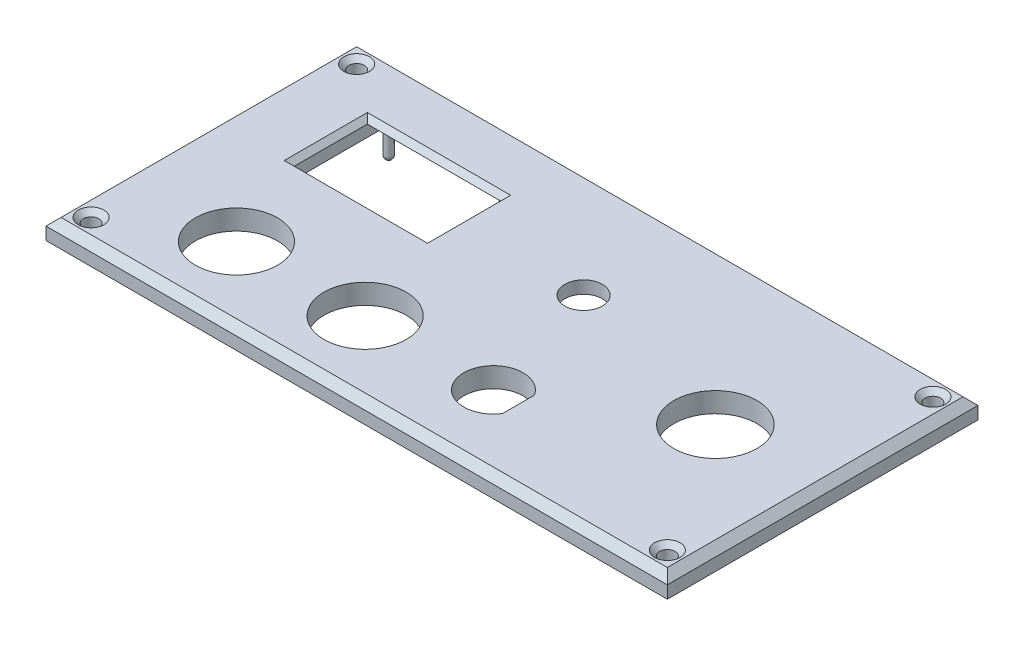
SolidWorks part; units mm, degrees
note: The reader was unsure of these and kept them because the rebuilt part matched: shared geometry of "Sketch2<3>", "Sketch2<4>", "Sketch2<5>".
ref_plane "Front Plane" through (0, 0, 0) normal (0, 0, 1) x (1, 0, 0)
ref_plane "Top Plane" through (0, 0, 0) normal (0, 1, 0) x (1, 0, 0)
ref_plane "Right Plane" through (0, 0, 0) normal (1, 0, 0) x (0, 0, -1)
sketch "Sketch2" plane through (0, 0, 0) normal (0, 1, 0) x (1, 0, 0)
  line L0 (-55.3925, 57.5) -> (145.2566, 57.5) construction
  line L1 (0, 0) -> (124, 0)
  line L2 (0, 0) -> (0, 62)
  line L3 (0, 62) -> (124, 62)
  line L4 (124, 0) -> (124, 62)
  line L5 (4.5, 83.9208) -> (4.5, -17.3547) construction
  line L6 (-55.3925, 4.5) -> (145.2566, 4.5) construction
  line L7 (119.5, 83.9208) -> (119.5, -17.3547) construction
  line L8 (3.6, 51.9) -> (3.6, 10.1)
  line L9 (-12.602, 31) -> (135.6682, 31) construction
  line L10 (135.6682, 31) -> (20.7736, 31) construction
  line L11 (10.1, 58.4) -> (113.9, 58.4)
  line L12 (3.6, 51.9) -> (10.1, 51.9)
  line L13 (3.6, 51.9) -> (3.6, 10.1)
  line L14 (3.6, 10.1) -> (10.1, 10.1)
  line L15 (120.4, 51.9) -> (120.4, 10.1)
  line L16 (62, 70.8482) -> (62, -22.3665) construction
  line L17 (113.9, 51.9) -> (120.4, 51.9)
  line L18 (10.1, 58.4) -> (113.9, 58.4)
  line L19 (10.1, 58.4) -> (10.1, 51.9)
  line L20 (10.1, 3.6) -> (113.9, 3.6)
  line L21 (113.9, 58.4) -> (113.9, 51.9)
  line L22 (10.1, 10.1) -> (10.1, 3.6)
  line L23 (113.9, 10.1) -> (120.4, 10.1)
  line L24 (113.9, 10.1) -> (113.9, 3.6)
  line L25 (79.4542, 18.0185) -> (79.4542, 11.6606)
  line L26 (14.9397, 49.1974) -> (41.5397, 49.1974)
  line L27 (14.9397, 49.1974) -> (14.9397, 34.5974)
  line L28 (14.9397, 34.5974) -> (41.5397, 34.5974)
  line L29 (41.5397, 49.1974) -> (41.5397, 34.5974)
  line L31 (14.2397, 53.7974) -> (42.2397, 53.7974)
  line L32 (14.2397, 53.7974) -> (14.2397, 25.4474)
  line L33 (14.2397, 25.4474) -> (42.2397, 25.4474)
  line L34 (42.2397, 53.7974) -> (42.2397, 25.4474)
  line L35 (60.4783, 47.2032) -> (73.6783, 47.2032)
  line L36 (60.4783, 47.2032) -> (60.4783, 33.2032)
  line L37 (60.4783, 33.2032) -> (73.6783, 33.2032)
  line L38 (73.6783, 47.2032) -> (73.6783, 33.2032)
  line L39 (60.4783, 47.2032) -> (73.6783, 33.2032) construction
  line L40 (60.4783, 33.2032) -> (73.6783, 47.2032) construction
  circle A0 centre (4.5, 57.5) radius 1.55
  circle A1 centre (119.5, 4.5) radius 1.55
  circle A2 centre (119.5, 57.5) radius 1.55
  circle A3 centre (4.5, 4.5) radius 1.55
  circle A4 centre (102.5933, 31) radius 8.3
  circle A5 centre (102.5933, 31) radius 12.375
  circle A6 centre (67.0783, 40.2032) radius 8.2
  circle A7 centre (67.0783, 40.2032) radius 3.75
  circle A8 centre (39.7997, 51.7093) radius 0.8
  circle A9 centre (39.7997, 28.4093) radius 0.8
  circle A10 centre (16.6797, 28.4093) radius 0.8
  circle A11 centre (16.6797, 51.7093) radius 0.8
  circle A12 centre (74.4542, 14.8396) radius 5.925
  circle A13 centre (74.4542, 14.8396) radius 7.25
  circle A14 centre (48.8465, 14.8396) radius 8.2
  circle A15 centre (48.8465, 14.8396) radius 8.95
  circle A16 centre (23.1711, 14.8396) radius 8.2
  circle A17 centre (23.1711, 14.8396) radius 8.95
  point P25 (0, 31)
  point P27 (3.6, 31)
  point P34 (62, 62)
  point P35 (62, 58.4)
  point P60 (64.5191, 39.9792)
  point P61 (28.2397, 34.5974)
  point P77 (28.2397, 53.7974)
  point P78 (28.2397, 49.1974)
  point P79 (67.0783, 40.2032)
  dimension "D7" = 3.1
  dimension "D14" = 16.6
  dimension "D15" = 24.75
  dimension "D16" = 16.4
  dimension "D17" = 7.5
  dimension "D20" = 1.6
  dimension "D21" = 23.3
  dimension "D25" = 11.85
  dimension "D26" = 14.5
  dimension "D28" = 28.35
  dimension "D22" = 13.2
  dimension "D1" = 62
  dimension "D2" = 124
  dimension "D3" = 4.5
  dimension "D4" = 4.5
  dimension "D5" = 4.5
  dimension "D6" = 4.5
  dimension "D8" = 41.8
  dimension "D9" = 3.6
  dimension "D10" = 3.6
  dimension "D11" = 103.8
  dimension "D12" = 3.6
  dimension "D13" = 3.6
  dimension "D18" = 14.6
  dimension "D19" = 26.6
  dimension "D23" = 11.56
  dimension "D24" = 11.56
  dimension "D27" = 5
  dimension "D29" = 28
  dimension "D30" = 4.6
  dimension "D31" = 14
extrude "Boss-Extrude1" add sketch "Sketch2" along normal blind 4 contours L24 L23 L15 L17 L21 L11 L19 L12 L8 L14 L22 L20 A17 A15 A13 A11 A10 A9 A8 A7 A5 L26 L29 L28 L27 | L1 L4 L3 L2 A3 A2 A1 A0 L23 L24 L20 L22 L14 L8 L12 L19 L11 L21 L17 L15 | A10 | A9 | A8 | A11 | L34 L31 L32 L33 A11 A10 A9 A8 L26 L29 L28 L27 | A13 A12 | A5 A4 | A7 A6 | A15 A14 | A17 A16 | L25 A12 | L36 A6 | L38 A6 | L35 A6 | L37 A6 | A6 L36 L37 | A6 L38 L35 | A6 L35 L36 | L37 A6 L38 L35 L36 A7
chamfer "Chamfer1" distance 1.5 angle 45 4 edges at (124, 4, -31) (62, 4, -62) (62, 4, 0) (0, 4, -31)
chamfer "Chamfer2" distance 1 angle 45 5 edges at (119.5, 4, -55.95) (119.5, 0, -55.95) (4.5, 4, -2.95) (119.5, 4, -2.95) (4.5, 4, -55.95)
extrude "Boss-Extrude2" add sketch "Sketch2<3>" against normal blind 3.5 contours A10 | A11 | A9 | A8
sketch "Sketch2<3>" plane through (0, 0, 0) normal (0, 1, 0) x (1, 0, 0) same geometry as "Sketch2"
fillet "Fillet1" radius 0.8 4 edges at (39.7997, -3.5, -27.6093) (16.6797, -3.5, -27.6093) (16.6797, -3.5, -50.9093) (39.7997, -3.5, -50.9093)
extrude "Cut-Extrude1" cut sketch "Sketch2<4>" along normal blind 3 contours L34 L31 L32 L33 A11 A10 A9 A8 L26 L29 L28 L27
sketch "Sketch2<4>" plane through (0, 0, 0) normal (0, 1, 0) x (1, 0, 0) same geometry as "Sketch2"
chamfer "Chamfer3" distance 1 angle 45 4 edges at (28.2397, 4, -34.5974) (41.5397, 4, -41.8974) (14.9397, 4, -41.8974) (28.2397, 4, -49.1974)
extrude "Cut-Extrude4" cut sketch "Sketch2<5>" along normal blind 1.5 contours L37 A6 L38 L35 L36 A7 | A6 L38 L35 | A6 L37 L38 | A6 L35 L36 | A6 L36 L37
sketch "Sketch2<5>" plane through (0, 0, 0) normal (0, 1, 0) x (1, 0, 0) same geometry as "Sketch2"
